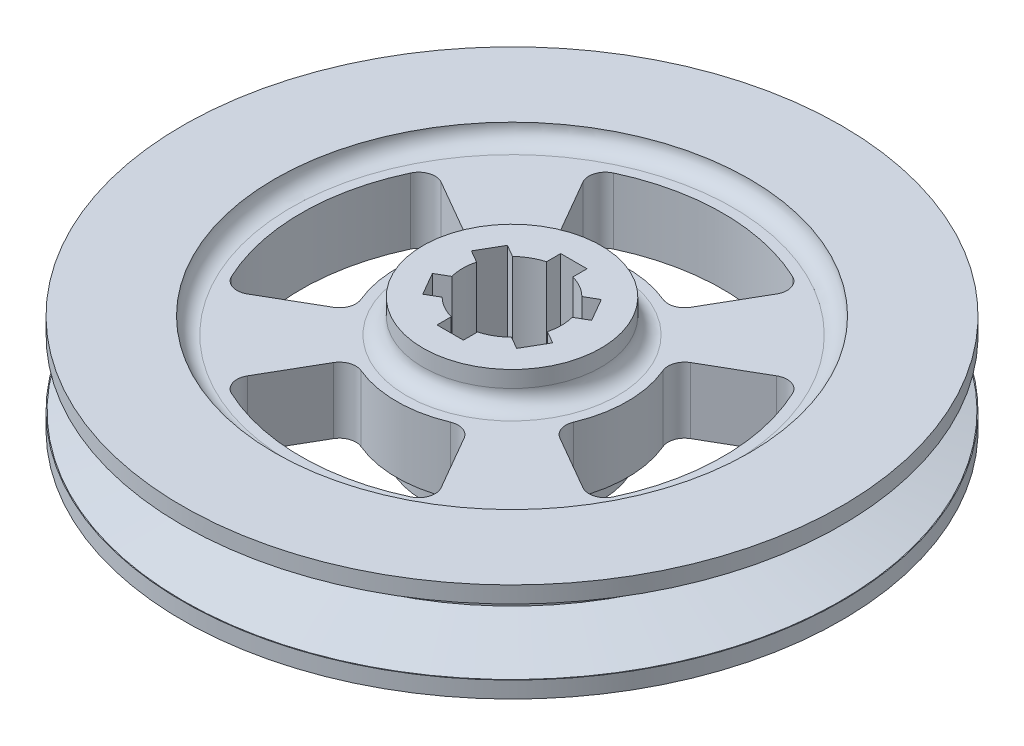
SolidWorks part; units mm, degrees
ref_plane "Front Plane" through (0, 0, 0) normal (0, 0, 1) x (1, 0, 0)
ref_plane "Top Plane" through (0, 0, 0) normal (0, 1, 0) x (1, 0, 0)
ref_plane "Right Plane" through (0, 0, 0) normal (1, 0, 0) x (0, 0, -1)
sketch "Sketch1" plane through (0, 0, 0) normal (0, 1, 0) x (1, 0, 0)
  line L0 (0, 142.7208) -> (0, 0) construction
  line L1 (-17.5, 30.3109) -> (-32, 55.4256)
  line L2 (17.5, 30.3109) -> (32, 55.4256)
  line L3 (30.3109, 17.5) -> (55.4256, 32)
  line L4 (30.3109, -17.5) -> (55.4256, -32)
  line L5 (17.5, -30.3109) -> (32, -55.4256)
  line L6 (-17.5, -30.3109) -> (-32, -55.4256)
  line L7 (-30.3109, -17.5) -> (-55.4256, -32)
  line L8 (-30.3109, 17.5) -> (-55.4256, 32)
  arc A0 (-55.4256, 32) -> (-55.4256, -32) centre (0, 0) ccw
  circle A1 centre (0, 0) radius 100
  arc A2 (-30.3109, 17.5) -> (-30.3109, -17.5) centre (0, 0) ccw
  arc A3 (-17.5, -30.3109) -> (17.5, -30.3109) centre (0, 0) ccw
  arc A4 (30.3109, -17.5) -> (30.3109, 17.5) centre (0, 0) ccw
  arc A5 (32, 55.4256) -> (-32, 55.4256) centre (0, 0) ccw
  arc A6 (17.5, 30.3109) -> (-17.5, 30.3109) centre (0, 0) ccw
  arc A7 (55.4256, -32) -> (55.4256, 32) centre (0, 0) ccw
  arc A8 (-32, -55.4256) -> (32, -55.4256) centre (0, 0) ccw
  point P25 (0, 0)
  dimension "D1" = 200
  dimension "D2" = 128
  dimension "D3" = 70
  dimension "D4" = 30
  dimension "D5" = 4
extrude "Boss-Extrude1" add sketch "Sketch1" along normal mid plane 20
sketch "Sketch2" plane through (0, 10, 0) normal (0, 1, 0) x (1, 0, 0)
  circle A0 centre (0, 0) radius 27
  dimension "D1" = 54
extrude "Boss-Extrude3" add sketch "Sketch2" along normal blind 10 and the other way blind 30
sketch "Sketch4" plane through (0, -10, 0) normal (0, -1, 0) x (1, 0, 0)
  circle A0 centre (0, 0) radius 27
  dimension "D1" = 54
extrude "Boss-Extrude4" add sketch "Sketch4" along normal mid plane 10
sketch "Sketch7" plane through (0, -10, 0) normal (0, -1, 0) x (1, 0, 0)
  circle A0 centre (0, 0) radius 100 construction
  circle A1 centre (0, 0) radius 100
  circle A2 centre (0, 0) radius 72
  dimension "D1" = 144
extrude "Boss-Extrude11" add sketch "Sketch7" along normal blind 5 and the other way blind 25
sketch "Sketch8" plane through (0, 20, 0) normal (0, 1, 0) x (1, 0, 0)
  line L0 (0, 27) -> (0, 0) construction
  line L1 (-4, 14.4568) -> (-4, 18.7628)
  line L2 (-4, 18.7628) -> (4, 18.7628)
  line L3 (4, 18.7628) -> (4, 14.4568)
  line L4 (10.52, 10.6925) -> (14.2491, 12.8455)
  line L5 (14.2491, 12.8455) -> (18.2491, 5.9173)
  line L6 (18.2491, 5.9173) -> (14.52, 3.7643)
  line L7 (14.52, -3.7643) -> (18.2491, -5.9173)
  line L8 (18.2491, -5.9173) -> (14.2491, -12.8455)
  line L9 (14.2491, -12.8455) -> (10.52, -10.6925)
  line L10 (4, -14.4568) -> (4, -18.7628)
  line L11 (4, -18.7628) -> (-4, -18.7628)
  line L12 (-4, -18.7628) -> (-4, -14.4568)
  line L13 (-10.52, -10.6925) -> (-14.2491, -12.8455)
  line L14 (-14.2491, -12.8455) -> (-18.2491, -5.9173)
  line L15 (-18.2491, -5.9173) -> (-14.52, -3.7643)
  line L16 (-14.52, 3.7643) -> (-18.2491, 5.9173)
  line L17 (-18.2491, 5.9173) -> (-14.2491, 12.8455)
  line L18 (-14.2491, 12.8455) -> (-10.52, 10.6925)
  arc A0 (-4, 14.4568) -> (-10.52, 10.6925) centre (0, 0) ccw
  circle A1 centre (0, 0) radius 27 construction
  circle A2 centre (0, 0) radius 27 construction
  arc A3 (10.52, 10.6925) -> (4, 14.4568) centre (0, 0) ccw
  arc A4 (14.52, -3.7643) -> (14.52, 3.7643) centre (0, 0) ccw
  arc A5 (4, -14.4568) -> (10.52, -10.6925) centre (0, 0) ccw
  arc A6 (-10.52, -10.6925) -> (-4, -14.4568) centre (0, 0) ccw
  arc A7 (-14.52, 3.7643) -> (-14.52, -3.7643) centre (0, 0) ccw
  point P34 (0, 0)
  dimension "D1" = 30
  dimension "D2" = 4
  dimension "D3" = 8
  dimension "D4" = 4
  dimension "D5" = 6
extrude "Cut-Extrude1" cut sketch "Sketch8" against normal through all
sketch "Sketch9" plane through (0, 0, 0) normal (1, 0, 0) x (0, 0, -1)
  line L0 (0, 78.1435) -> (0, 0) construction
  line L1 (-80, 0) -> (-136.9864, 0) construction
  line L4 (-80, 4.71) -> (-80, -4.71)
  line L9 (-80, 4.71) -> (-99.7755, 10.0088)
  line L13 (-99.8394, 9.9781) -> (-116.2467, 9.9781)
  line L14 (-80, -4.71) -> (-99.7755, -10.0088)
  line L15 (-80, 0) -> (0, 0) construction
  line L16 (-99.8394, 9.9781) -> (-99.7755, 10.0088)
  line L17 (-116.2467, 9.9781) -> (-116.2467, -10.0088)
  line L18 (-116.2467, -10.0088) -> (-99.7755, -10.0088)
  point P10 (-110.2686, 0)
  point P11 (-111.2764, 0)
  point P14 (-80, 0)
  dimension "D1" = 80
  dimension "D2" = 15
  dimension "D3" = 4.71
  dimension "D4" = 9.42
revolve "Cut-Revolve4" cut sketch "Sketch9" angle 360 about L0
fillet "Fillet1" radius 5 4 edges at (0, 10, 27) (0, 10, 72) (0, -10, 27) (0, -10, 72)
fillet "Fillet2" radius 5 16 edges at (30.3109, 0, -17.5) (55.4256, 0, -32) (32, 0, -55.4256) (55.4256, 0, 32) (17.5, 0, -30.3109) (-17.5, 0, -30.3109) (-30.3109, 0, -17.5) (-30.3109, 0, 17.5) (-32, 0, -55.4256) (32, 0, 55.4256) (30.3109, 0, 17.5) (-32, 0, 55.4256) (-55.4256, 0, 32) (17.5, 0, 30.3109) (-17.5, 0, 30.3109) (-55.4256, 0, -32)
